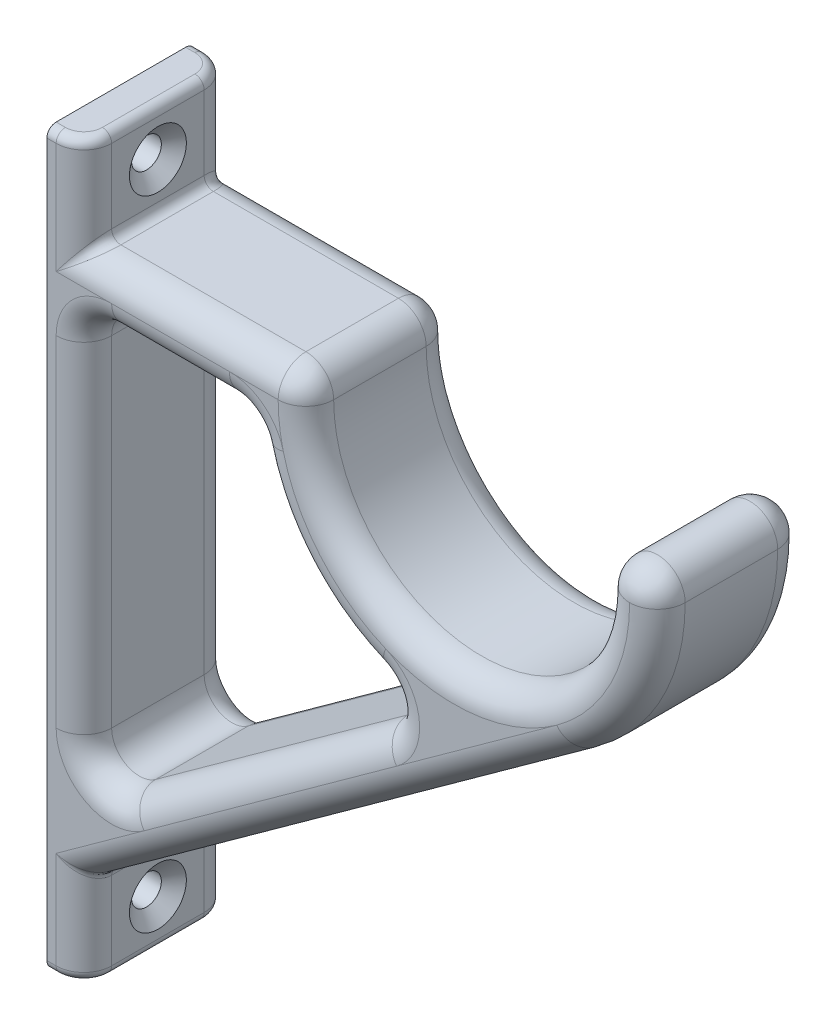
SolidWorks part; units mm, degrees
ref_plane "Front Plane" through (0, 0, 0) normal (0, 0, 1) x (1, 0, 0)
ref_plane "Top Plane" through (0, 0, 0) normal (0, 1, 0) x (1, 0, 0)
ref_plane "Right Plane" through (0, 0, 0) normal (1, 0, 0) x (0, 0, -1)
sketch "Sketch1" plane through (0, 0, 0) normal (0, 0, 1) x (1, 0, 0)
  line L5 (25.4, 0) -> (34.925, 0) construction
  line L6 (14.8646, -20.5962) -> (20.4389, -28.3197) construction
  line L7 (-25.4, 0) -> (-69.85, 0) construction
  line L8 (20.4389, -28.3197) -> (-63.5, -88.9)
  line L9 (-63.5, -88.9) -> (-63.5, -104.775)
  line L10 (-63.5, -104.775) -> (-69.85, -104.775)
  line L11 (-69.85, -104.775) -> (-69.85, 0)
  line L13 (-63.5, 4.7625) -> (-30.1625, 4.7625)
  line L14 (-34.5988, -4.7625) -> (-63.5, -4.7625)
  line L15 (-4.5726, -34.6244) -> (-63.5, -77.1534)
  line L16 (-63.5, -4.7625) -> (-63.5, -77.1534)
  line L17 (-69.85, 0) -> (-69.85, 20.6375)
  line L18 (-69.85, 20.6375) -> (-63.5, 20.6375)
  line L19 (-63.5, 20.6375) -> (-63.5, 4.7625)
  arc A0 (25.4, 0) -> (-25.4, 0) centre (0, 0) cw
  arc A3 (34.925, 0) -> (20.4389, -28.3197) centre (0, 0) cw
  arc A4 (25.4, 0) -> (34.925, 0) centre (30.1625, 0) cw
  arc A6 (-25.4, 0) -> (-30.1625, 4.7625) centre (-30.1625, 0) ccw
  arc A7 (-4.5726, -34.6244) -> (-34.5988, -4.7625) centre (0, 0) cw
  point P16 (-52.6363, 4.7625)
  dimension "D1" = 25.4
  dimension "D3" = 9.525
  dimension "D2" = 88.9
  dimension "D4" = 69.85
  dimension "D5" = 4.7625
  dimension "D6" = 6.35
  dimension "D7" = 15.875
extrude "Boss-Extrude1" add sketch "Sketch1" along normal mid plane 25.4
fillet "Fillet1" radius 4.7625 28 edges at (-21.5306, -58.6099, 12.7) (31.0933, -15.9048, 12.7) (30.1625, 4.7625, 12.7) (0, -25.4, 12.7) (-26.7949, 3.3676, 12.7) (-21.5306, -58.6099, -12.7) (31.0933, -15.9048, -12.7) (30.1625, 4.7625, -12.7) (-46.8313, 4.7625, -12.7) (-26.7949, 3.3676, -12.7) (-4.5726, -34.6244, 0) (-34.5988, -4.7625, 0) (-63.5, -4.7625, 0) (-63.5, -77.1534, 0) (-46.8313, 4.7625, 12.7) (0, -25.4, -12.7) (-24.6279, -24.7634, -12.7) (-63.5, -40.958, 12.7) (-49.0494, -4.7625, -12.7) (-34.0363, -55.8889, -12.7) (-34.0363, -55.8889, 12.7) (-49.0494, -4.7625, 12.7) (-63.5, -40.958, -12.7) (-24.6279, -24.7634, 12.7) (-63.5, -96.8375, -12.7) (-63.5, -96.8375, 12.7) (-63.5, 12.7, -12.7) (-63.5, 12.7, 12.7)
sketch "Sketch2" plane through (-63.5, 0, 0) normal (1, 0, 0) x (0, 0, -1)
  line L0 (-7.9375, 20.6375) -> (7.9375, 4.7625) construction
  line L1 (-7.9375, -104.775) -> (7.9375, -88.9) construction
  point P8 (0, 12.7)
  point P9 (0, -96.8375)
hole_wizard "CSK for #10 Flat Head Machine Screw (100)1" positions "3DSketch1" profile "Sketch3" countersink size "#10" standard "ANSI Inch" end condition up to next
sketch3d "3DSketch1"
  point P0 (-63.5, 12.7, 0)
  point P3 (-63.5, -96.8375, 0)
sketch "Sketch3" plane through (-63.5, 12.7, 0) normal (0, 1, 0) x (0, 0, -1)
  line L0 (0, 0) -> (0, 6.35)
  line L1 (0, 6.35) -> (2.5527, 6.35)
  line L2 (2.5527, 6.35) -> (2.5527, 1.9608)
  line L3 (2.5527, 1.9608) -> (4.8895, 0)
  line L5 (4.8895, 0) -> (0, 0)
  line L6 (-2.5527, 1.9608) -> (-4.8895, 0) construction
  line L11 (0, -6.35) -> (0, 107.95) construction
  dimension "Thru Hole Dia." = 5.1054
  dimension "Thru Hole Depth" = 6.35
  dimension "Near C'Sink Dia." = 9.779
  dimension "Near C'Sink Angle" = 100
fillet "Fillet2" radius 1.5875 16 edges at (-64.8949, 3.3676, 11.3051) (-64.8949, 3.3676, -11.3051) (-64.8949, -88.1865, 11.3051) (-64.8949, -88.1865, -11.3051) (-69.0563, -104.775, 12.7) (-64.8949, -104.775, 11.3051) (-69.0563, -104.775, -12.7) (-64.8949, -104.775, -11.3051) (-69.0563, 20.6375, 12.7) (-64.8949, 20.6375, 11.3051) (-69.0563, 20.6375, -12.7) (-64.8949, 20.6375, -11.3051) (-63.5, 4.7625, 0) (-63.5, -88.9, 0) (-63.5, -104.775, 0) (-63.5, 20.6375, 0)
